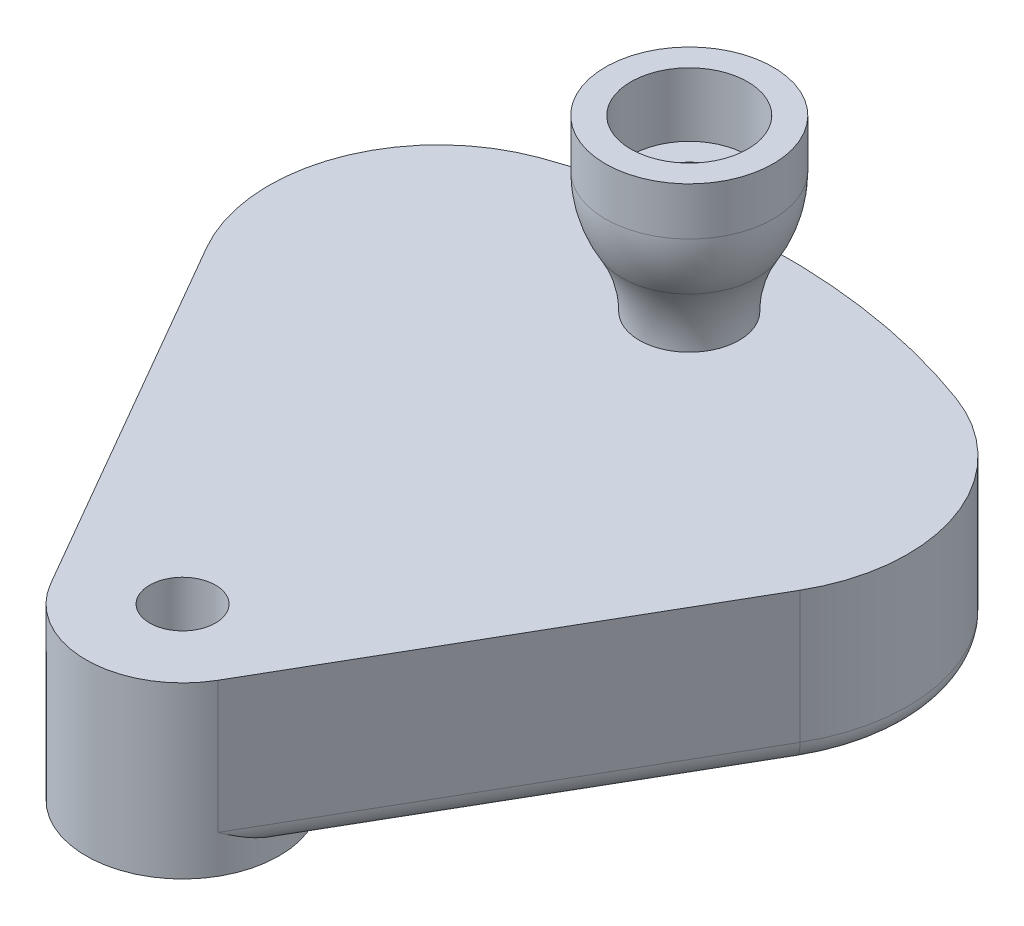
SolidWorks part; units mm, degrees
other "Support Blade"
other "Knob"
ref_plane "Front Plane" through (0, 0, 0) normal (0, 0, 1) x (1, 0, 0)
ref_plane "Top Plane" through (0, 0, 0) normal (0, 1, 0) x (1, 0, 0)
ref_plane "Right Plane" through (0, 0, 0) normal (1, 0, 0) x (0, 0, -1)
sketch "Sketch1" plane through (0, 0, 0) normal (0, 1, 0) x (1, 0, 0)
  line L0 (0, 0) -> (0, 28.3673) construction
  line L1 (-17.9404, 21.9737) -> (-3.9404, -2.275)
  line L2 (3.9404, -2.275) -> (17.9404, 21.9737)
  circle A0 centre (0, 0) radius 1.55
  arc A1 (-17.9404, 21.9737) -> (17.9404, 21.9737) centre (0, 0) cw
  arc A2 (-3.9404, -2.275) -> (3.9404, -2.275) centre (0, 0) ccw
  dimension "D1" = 3.1
  dimension "D4" = 3
  dimension "D2" = 60
  dimension "D3" = 28
extrude "Boss-Extrude1" add sketch "Sketch1" along normal blind 8
fillet "Fillet1" radius 8 2 edges at (-17.9404, 4, -21.9737) (17.9404, 4, -21.9737)
chamfer "Chamfer1" distance 3 angle 20 6 edges at (-14.5721, 0, -21.8286) (-8.9587, 0, -6.4168) (0, 0, -28.3673) (0, 0, 4.55) (14.5721, 0, -21.8286) (8.9587, 0, -6.4168) first distance on face at (0, 0, -13.3847)
sketch "Sketch2" plane through (0, 8, 0) normal (0, 1, 0) x (1, 0, 0)
  circle A0 centre (0, 0) radius 4.55
  circle A1 centre (0, 0) radius 1.55 construction
  circle A2 centre (0, 0) radius 1.55
  arc A3 (-3.9404, -2.275) -> (3.9404, -2.275) centre (0, 0) ccw construction
extrude "Boss-Extrude2" add sketch "Sketch2" against normal blind 8
fillet "Fillet2" radius 1 10 edges at (-7.43, 0, -9.7692) (-11.7508, 0, -20.8086) (0, 0, -25.3673) (11.7508, 0, -20.8086) (-8.9587, 1.0919, -6.4168) (-14.5721, 1.0919, -21.8286) (0, 1.0919, -28.3673) (14.5721, 1.0919, -21.8286) (7.43, 0, -9.7692) (8.9587, 1.0919, -6.4168)
sketch "Sketch3" plane through (0, 8, 0) normal (0, 1, 0) x (1, 0, 0)
  line L0 (-19.6482, 28.3673) -> (36.5809, 28.3673) construction
  line L1 (0, 41.9401) -> (0, -7.1006) construction
  circle A0 centre (0, 23.8673) radius 1.25
  arc A2 (9.8173, 26.6143) -> (-9.8173, 26.6143) centre (0, 0) ccw construction
  dimension "D1" = 2.5
  dimension "D2" = 4.5
extrude "Cut-Extrude1" cut sketch "Sketch3" against normal through all
sketch "Sketch4" plane through (0, 0, 0) normal (1, 0, 0) x (0, 0, -1)
  line L0 (23.8673, 15.4876) -> (23.8673, -4.1268) construction
  line L1 (28.3673, 15.4876) -> (28.3673, -6.7163) construction
  line L2 (28.3673, 1.7921) -> (28.3673, 8) construction
  line L3 (23.8673, 0) -> (23.8673, 8) construction
  line L4 (25.4173, 8) -> (26.2173, 8)
  line L5 (26.6143, 8) -> (15.1087, 8) construction
  line L6 (27.8173, 13.749) -> (27.8173, 16)
  line L7 (27.8173, 16) -> (26.6173, 16)
  line L8 (26.6173, 16) -> (26.6173, 13)
  line L9 (26.6173, 13) -> (25.4173, 13)
  line L10 (25.4173, 13) -> (25.4173, 8)
  arc A0 (26.2173, 8) -> (27.0398, 10.9553) centre (31.9379, 8) cw
  arc A1 (27.0398, 10.9553) -> (27.8173, 13.749) centre (22.4094, 13.749) ccw
  dimension "D1" = 0.8
  dimension "D2" = 1.2
  dimension "D3" = 13
  dimension "D4" = 5.5
  dimension "D5" = 3.1
  dimension "D6" = 3
revolve "Revolve1" add sketch "Sketch4" angle 360 about L0
